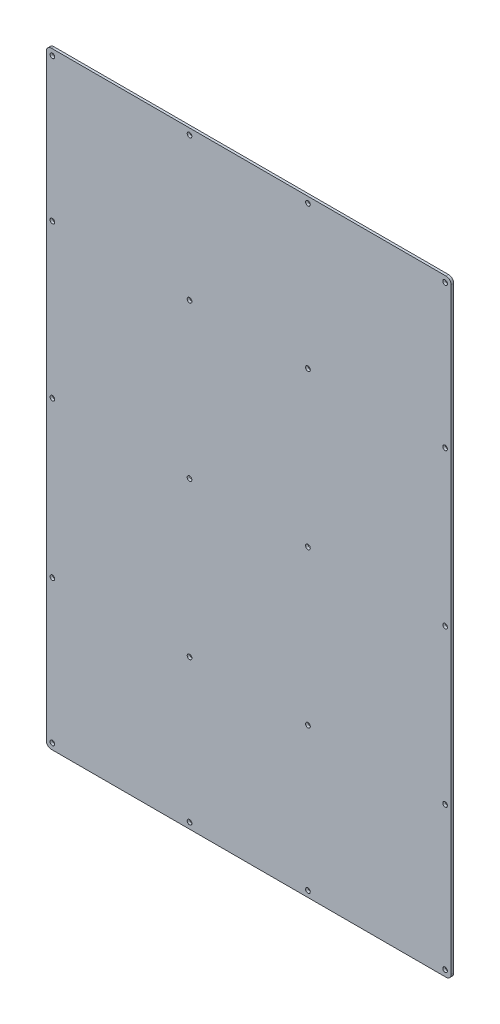
SolidWorks part; units mm, degrees
ref_plane "Front Plane" through (0, 0, 0) normal (0, 0, 1) x (1, 0, 0)
ref_plane "Top Plane" through (0, 0, 0) normal (0, 1, 0) x (1, 0, 0)
ref_plane "Right Plane" through (0, 0, 0) normal (1, 0, 0) x (0, 0, -1)
sketch "Sketch1" plane through (0, 0, 0) normal (0, 0, 1) x (1, 0, 0)
  line L1 (0, 0) -> (254, 0)
  line L2 (0, 0) -> (0, 381)
  line L3 (0, 381) -> (254, 381)
  line L4 (254, 0) -> (254, 381)
  dimension "D1" = 381
  dimension "D2" = 254
extrude "Boss-Extrude1" add sketch "Sketch1" along normal blind 1.5875
sketch "Sketch2" plane through (0, 0, 1.5875) normal (0, 0, 1) x (1, 0, 0)
  line L0 (89.8652, 377.19) -> (89.8652, 3.81) construction
  line L1 (0, 381) -> (254, 381) construction
  line L2 (127, 381) -> (127, 377.19) construction
  line L3 (3.81, 377.19) -> (250.19, 377.19) construction
  line L5 (164.1348, 377.19) -> (164.1348, 3.81) construction
  line L6 (3.81, 377.19) -> (3.81, 3.81) construction
  line L7 (3.81, 3.81) -> (250.19, 3.81) construction
  line L8 (250.19, 3.81) -> (250.19, 377.19) construction
  line L9 (3.81, 190.5) -> (250.19, 190.5) construction
  line L10 (3.81, 287.3756) -> (250.19, 287.3756) construction
  line L11 (3.81, 93.6244) -> (250.19, 93.6244) construction
  line L12 (0, 381) -> (0, 0) construction
  line L13 (0, 190.5) -> (3.81, 190.5) construction
  circle A0 centre (3.81, 377.19) radius 1.4732
  circle A1 centre (89.8652, 377.19) radius 1.4732
  circle A2 centre (164.1348, 377.19) radius 1.4732
  circle A3 centre (250.19, 377.19) radius 1.4732
  circle A4 centre (164.1348, 287.3755) radius 1.4732
  circle A5 centre (3.81, 287.3756) radius 1.4732
  circle A6 centre (250.19, 287.3756) radius 1.4732
  circle A7 centre (89.8652, 287.3756) radius 1.4732
  circle A8 centre (164.1348, 190.5) radius 1.4732
  circle A9 centre (3.81, 191.135) radius 1.4732
  circle A10 centre (250.19, 190.5) radius 1.4732
  circle A11 centre (89.8652, 190.5) radius 1.4732
  circle A12 centre (164.1348, 93.6244) radius 1.4732
  circle A13 centre (3.81, 93.6244) radius 1.4732
  circle A14 centre (250.19, 93.6244) radius 1.4732
  circle A15 centre (89.8652, 93.6244) radius 1.4732
  circle A16 centre (164.1348, 3.81) radius 1.4732
  circle A17 centre (3.81, 3.81) radius 1.4732
  circle A18 centre (250.19, 3.81) radius 1.4732
  circle A19 centre (89.8652, 3.81) radius 1.4732
  dimension "D6" = 2.9464
  dimension "D23" = 0
  dimension "D24" = 0
  dimension "D25" = 0
  dimension "D28" = 0
  dimension "D29" = 0
  dimension "D30" = 0
  dimension "D31" = 0
  dimension "D32" = 86.0552
  dimension "D1" = 246.38
  dimension "D3" = 373.38
  dimension "D4" = 96.8756
  dimension "D5" = 96.8756
  dimension "D7" = 86.0552
  dimension "D8" = 86.0552
  dimension "D9" = 0
  dimension "D10" = 0
  dimension "D11" = 0
  dimension "D12" = 86.0552
  dimension "D13" = 0
  dimension "D14" = 0
  dimension "D15" = 0
  dimension "D16" = 0
  dimension "D17" = 0
  dimension "D18" = 0
  dimension "D19" = 0
  dimension "D20" = 0
  dimension "D21" = 0
  dimension "D22" = 0
  dimension "D26" = 0
  dimension "D27" = 0
extrude "Cut-Extrude1" cut sketch "Sketch2" against normal through all
fillet "Fillet1" radius 3.175 4 edges at (254, 0, 0.7937) (0, 0, 0.7937) (254, 381, 0.7937) (0, 381, 0.7937)
